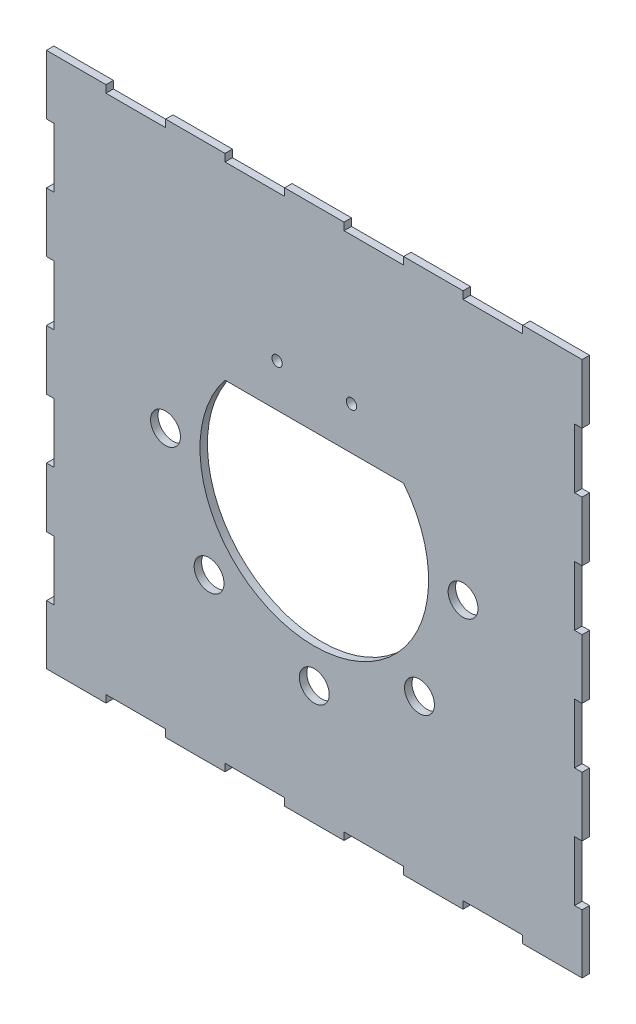
SolidWorks part; units mm, degrees
ref_plane "Front Plane" through (0, 0, 0) normal (0, 0, 1) x (1, 0, 0)
ref_plane "Top Plane" through (0, 0, 0) normal (0, 1, 0) x (1, 0, 0)
ref_plane "Right Plane" through (0, 0, 0) normal (1, 0, 0) x (0, 0, -1)
sketch "Sketch1" plane through (0, 0, 0) normal (0, 0, 1) x (1, 0, 0)
  line L0 (57.15, -57.15) -> (-57.15, 57.15) construction
  line L1 (-57.15, -57.15) -> (57.15, -57.15)
  line L2 (-57.15, -57.15) -> (-57.15, 57.15)
  line L3 (-57.15, 57.15) -> (57.15, 57.15)
  line L4 (57.15, -57.15) -> (57.15, 57.15)
  line L5 (-57.15, -57.15) -> (57.15, 57.15) construction
  point P0 (0, 0)
  point P6 (0, 0)
  dimension "D2" = 114.3
  dimension "D3" = 114.3
extrude "Boss-Extrude1" add sketch "Sketch1" along normal blind 1.5875
sketch "Sketch2" plane through (0, 0, 1.5875) normal (0, 0, 1) x (1, 0, 0)
  line L0 (-19.05, 15.24) -> (19.05, 15.24) construction
  line L1 (0, 15.24) -> (0, 0) construction
  line L2 (-19.05, 15.24) -> (19.05, 15.24)
  circle A0 centre (0, 0) radius 24.3959 construction
  arc A1 (-19.05, 15.24) -> (19.05, 15.24) centre (0, 0) ccw
  dimension "D1" = 38.1
  dimension "D2" = 15.24
extrude "Cut-Extrude1" cut sketch "Sketch2" against normal through all
sketch "Sketch4" plane through (0, 0, 1.5875) normal (0, 0, 1) x (1, 0, 0)
  line L0 (-31.75, 0) -> (31.75, 0) construction
  line L1 (0, 0) -> (-22.4506, -22.4506) construction
  line L2 (0, 0) -> (0, -31.75) construction
  line L3 (0, 0) -> (22.4506, -22.4506) construction
  circle A0 centre (0, 0) radius 31.75 construction
  circle A1 centre (-31.75, 0) radius 3.1877
  circle A2 centre (-22.4506, -22.4506) radius 3.1877
  circle A3 centre (0, -31.75) radius 3.1877
  circle A4 centre (22.4506, -22.4506) radius 3.1877
  circle A5 centre (31.75, 0) radius 3.1877
  point P6 (0, 0)
  dimension "D1" = 63.5
  dimension "D4" = 6.3754
  dimension "D2" = 45
  dimension "D3" = 45
extrude "Cut-Extrude2" cut sketch "Sketch4" against normal through all
sketch "Sketch6" plane through (0, 0, 1.5875) normal (0, 0, 1) x (1, 0, 0)
  line L20 (-57.15, 57.15) -> (-57.15, 44.45) construction
  line L21 (-57.15, 57.15) -> (-57.15, -57.15) construction
  line L22 (-57.15, 19.0246) -> (-57.15, 6.2992)
  line L23 (-57.15, 44.45) -> (-55.56, 44.45)
  line L24 (-57.15, 44.45) -> (-57.15, 31.7246)
  line L25 (-57.15, 31.7246) -> (-55.56, 31.7246)
  line L26 (-55.56, 44.45) -> (-55.56, 31.7246)
  line L27 (-57.15, 19.0246) -> (-55.56, 19.0246)
  line L28 (-55.56, 19.0246) -> (-55.56, 6.2992)
  line L29 (-57.15, 6.2992) -> (-55.56, 6.2992)
  line L30 (-57.15, -6.4008) -> (-57.15, -19.1262)
  line L31 (-57.15, -6.4008) -> (-55.56, -6.4008)
  line L32 (-55.56, -6.4008) -> (-55.56, -19.1262)
  line L33 (-57.15, -19.1262) -> (-55.56, -19.1262)
  line L34 (-57.15, -31.8262) -> (-57.15, -44.5516)
  line L35 (-57.15, -31.8262) -> (-55.56, -31.8262)
  line L36 (-55.56, -31.8262) -> (-55.56, -44.5516)
  line L37 (-57.15, -44.5516) -> (-55.56, -44.5516)
  line L38 (-57.15, 57.15) -> (-44.45, 57.15) construction
  line L39 (-55.56, 31.7246) -> (-55.56, 19.0246) construction
  line L60 (57.15, 57.15) -> (-57.15, 57.15) construction
  line L61 (57.15, 57.15) -> (57.15, 44.45) construction
  line L62 (57.15, -57.15) -> (57.15, 57.15) construction
  line L63 (57.15, 19.0246) -> (57.15, 6.2992)
  line L64 (57.15, 44.45) -> (55.56, 44.45)
  line L65 (57.15, 44.45) -> (57.15, 31.7246)
  line L66 (57.15, 31.7246) -> (55.56, 31.7246)
  line L67 (55.56, 44.45) -> (55.56, 31.7246)
  line L68 (57.15, 19.0246) -> (55.56, 19.0246)
  line L69 (55.56, 19.0246) -> (55.56, 6.2992)
  line L70 (57.15, 6.2992) -> (55.56, 6.2992)
  line L71 (57.15, -6.4008) -> (57.15, -19.1262)
  line L72 (57.15, -6.4008) -> (55.56, -6.4008)
  line L73 (55.56, -6.4008) -> (55.56, -19.1262)
  line L74 (57.15, -19.1262) -> (55.56, -19.1262)
  line L75 (57.15, -31.8262) -> (57.15, -44.5516)
  line L76 (57.15, -31.8262) -> (55.56, -31.8262)
  line L77 (55.56, -31.8262) -> (55.56, -44.5516)
  line L78 (57.15, -44.5516) -> (55.56, -44.5516)
  line L79 (55.56, 31.7246) -> (55.56, 19.0246) construction
  line L80 (-19.05, 57.15) -> (-19.05, 55.56)
  line L81 (-44.45, 57.15) -> (-31.7246, 57.15)
  line L82 (-44.45, 57.15) -> (-44.45, 55.56)
  line L83 (-44.45, 55.56) -> (-31.7246, 55.56)
  line L84 (-31.7246, 57.15) -> (-31.7246, 55.56)
  line L85 (-19.05, 57.15) -> (-6.3246, 57.15)
  line L86 (-6.3246, 57.15) -> (-6.3246, 55.56)
  line L87 (-19.05, 55.56) -> (-6.3246, 55.56)
  line L88 (6.35, 57.15) -> (6.35, 55.56)
  line L89 (6.35, 57.15) -> (19.0754, 57.15)
  line L90 (19.0754, 57.15) -> (19.0754, 55.56)
  line L91 (6.35, 55.56) -> (19.0754, 55.56)
  line L92 (31.75, 57.15) -> (31.75, 55.56)
  line L93 (31.75, 57.15) -> (44.4754, 57.15)
  line L94 (44.4754, 57.15) -> (44.4754, 55.56)
  line L95 (31.75, 55.56) -> (44.4754, 55.56)
  line L96 (-31.7246, 57.15) -> (-19.05, 57.15) construction
  line L97 (-57.15, -57.15) -> (-44.45, -57.15) construction
  line L98 (-57.15, -57.15) -> (57.15, -57.15) construction
  line L99 (-19.05, -57.15) -> (-19.05, -55.56)
  line L100 (-44.45, -57.15) -> (-31.7246, -57.15)
  line L101 (-44.45, -57.15) -> (-44.45, -55.56)
  line L102 (-44.45, -55.56) -> (-31.7246, -55.56)
  line L103 (-31.7246, -57.15) -> (-31.7246, -55.56)
  line L104 (-19.05, -57.15) -> (-6.3246, -57.15)
  line L105 (-6.3246, -57.15) -> (-6.3246, -55.56)
  line L106 (-19.05, -55.56) -> (-6.3246, -55.56)
  line L107 (6.35, -57.15) -> (6.35, -55.56)
  line L108 (6.35, -57.15) -> (19.0754, -57.15)
  line L109 (19.0754, -57.15) -> (19.0754, -55.56)
  line L110 (6.35, -55.56) -> (19.0754, -55.56)
  line L111 (31.75, -57.15) -> (31.75, -55.56)
  line L112 (31.75, -57.15) -> (44.4754, -57.15)
  line L113 (44.4754, -57.15) -> (44.4754, -55.56)
  line L114 (31.75, -55.56) -> (44.4754, -55.56)
  line L115 (-31.7246, -55.56) -> (-19.05, -55.56) construction
  dimension "D2" = 12.7
  dimension "D4" = 12.7
  dimension "D5" = 12.7254
  dimension "D6" = 1.59
  dimension "D8" = 12.7254
  dimension "D9" = 12.7
  dimension "D10" = 4
  dimension "D11" = 12.6746
  dimension "D13" = 12.7
  dimension "D14" = 1.59
  dimension "D15" = 12.7254
  dimension "D16" = 1.59
  dimension "D18" = 12.7
  dimension "D3" = 1.59
  dimension "D12" = 12.7
  dimension "D19" = 12.7254
  dimension "D21" = 12.6746
  dimension "D7" = 4
  dimension "D17" = 4
  dimension "D20" = 4
extrude "Cut-Extrude5" cut sketch "Sketch6" against normal through all
sketch "Sketch7" plane through (0, 0, 1.5875) normal (0, 0, 1) x (1, 0, 0)
  line L0 (19.05, 15.24) -> (-19.05, 15.24) construction
  line L1 (19.05, 15.24) -> (-19.05, 15.24) construction
  line L2 (0, 15.24) -> (0, 24.3675) construction
  line L3 (-7.9375, 24.3675) -> (7.9375, 24.3675) construction
  line L68 (-55.56, 44.45) -> (-55.56, 31.7246)
  line L69 (-55.56, 31.7246) -> (-57.15, 31.7246)
  line L70 (-57.15, 31.7246) -> (-57.15, 19.0246)
  line L71 (-57.15, 19.0246) -> (-55.56, 19.0246)
  line L72 (-55.56, 19.0246) -> (-55.56, 6.2992)
  line L73 (-55.56, 6.2992) -> (-57.15, 6.2992)
  line L74 (-57.15, 6.2992) -> (-57.15, -6.4008)
  line L75 (-57.15, -6.4008) -> (-55.56, -6.4008)
  line L76 (-55.56, -6.4008) -> (-55.56, -19.1262)
  line L77 (-55.56, -19.1262) -> (-57.15, -19.1262)
  line L78 (-57.15, -19.1262) -> (-57.15, -31.8262)
  line L79 (-57.15, -31.8262) -> (-55.56, -31.8262)
  line L80 (-55.56, -31.8262) -> (-55.56, -44.5516)
  line L81 (-55.56, -44.5516) -> (-57.15, -44.5516)
  line L82 (-57.15, -44.5516) -> (-57.15, -57.15)
  line L83 (-57.15, -57.15) -> (-44.45, -57.15)
  line L84 (-44.45, -57.15) -> (-44.45, -55.56)
  line L85 (-44.45, -55.56) -> (-31.7246, -55.56)
  line L86 (-31.7246, -55.56) -> (-31.7246, -57.15)
  line L87 (-31.7246, -57.15) -> (-19.05, -57.15)
  line L88 (-19.05, -57.15) -> (-19.05, -55.56)
  line L89 (-19.05, -55.56) -> (-6.3246, -55.56)
  line L90 (-6.3246, -55.56) -> (-6.3246, -57.15)
  line L91 (-6.3246, -57.15) -> (6.35, -57.15)
  line L92 (6.35, -57.15) -> (6.35, -55.56)
  line L93 (6.35, -55.56) -> (19.0754, -55.56)
  line L94 (19.0754, -55.56) -> (19.0754, -57.15)
  line L95 (19.0754, -57.15) -> (31.75, -57.15)
  line L96 (31.75, -57.15) -> (31.75, -55.56)
  line L97 (31.75, -55.56) -> (44.4754, -55.56)
  line L98 (44.4754, -55.56) -> (44.4754, -57.15)
  line L99 (44.4754, -57.15) -> (57.15, -57.15)
  line L100 (57.15, -57.15) -> (57.15, -44.5516)
  line L101 (57.15, -44.5516) -> (55.56, -44.5516)
  line L102 (55.56, -44.5516) -> (55.56, -31.8262)
  line L103 (55.56, -31.8262) -> (57.15, -31.8262)
  line L104 (57.15, -31.8262) -> (57.15, -19.1262)
  line L105 (57.15, -19.1262) -> (55.56, -19.1262)
  line L106 (55.56, -19.1262) -> (55.56, -6.4008)
  line L107 (55.56, -6.4008) -> (57.15, -6.4008)
  line L108 (57.15, -6.4008) -> (57.15, 6.2992)
  line L109 (57.15, 6.2992) -> (55.56, 6.2992)
  line L110 (55.56, 6.2992) -> (55.56, 19.0246)
  line L111 (55.56, 19.0246) -> (57.15, 19.0246)
  line L112 (57.15, 19.0246) -> (57.15, 31.7246)
  line L113 (57.15, 31.7246) -> (55.56, 31.7246)
  line L114 (55.56, 31.7246) -> (55.56, 44.45)
  line L115 (55.56, 44.45) -> (57.15, 44.45)
  line L116 (57.15, 44.45) -> (57.15, 57.15)
  line L117 (57.15, 57.15) -> (44.4754, 57.15)
  line L118 (44.4754, 57.15) -> (44.4754, 55.56)
  line L119 (44.4754, 55.56) -> (31.75, 55.56)
  line L120 (31.75, 55.56) -> (31.75, 57.15)
  line L121 (31.75, 57.15) -> (19.0754, 57.15)
  line L122 (19.0754, 57.15) -> (19.0754, 55.56)
  line L123 (19.0754, 55.56) -> (6.35, 55.56)
  line L124 (6.35, 55.56) -> (6.35, 57.15)
  line L125 (6.35, 57.15) -> (-6.3246, 57.15)
  line L126 (-6.3246, 57.15) -> (-6.3246, 55.56)
  line L127 (-6.3246, 55.56) -> (-19.05, 55.56)
  line L128 (-19.05, 55.56) -> (-19.05, 57.15)
  line L129 (-19.05, 57.15) -> (-31.7246, 57.15)
  line L130 (-31.7246, 57.15) -> (-31.7246, 55.56)
  line L131 (-31.7246, 55.56) -> (-44.45, 55.56)
  line L132 (-44.45, 55.56) -> (-44.45, 57.15)
  line L133 (-44.45, 57.15) -> (-57.15, 57.15)
  line L134 (-57.15, 57.15) -> (-57.15, 44.45)
  line L135 (-57.15, 44.45) -> (-55.56, 44.45)
  line L136 (-55.56, 44.45) -> (-55.56, 31.7246)
  line L137 (-55.56, 31.7246) -> (-57.15, 31.7246)
  line L138 (-57.15, 31.7246) -> (-57.15, 19.0246)
  line L139 (-57.15, 19.0246) -> (-55.56, 19.0246)
  line L140 (-55.56, 19.0246) -> (-55.56, 6.2992)
  line L141 (-55.56, 6.2992) -> (-57.15, 6.2992)
  line L142 (-57.15, 6.2992) -> (-57.15, -6.4008)
  line L143 (-57.15, -6.4008) -> (-55.56, -6.4008)
  line L144 (-55.56, -6.4008) -> (-55.56, -19.1262)
  line L145 (-55.56, -19.1262) -> (-57.15, -19.1262)
  line L146 (-57.15, -19.1262) -> (-57.15, -31.8262)
  line L147 (-57.15, -31.8262) -> (-55.56, -31.8262)
  line L148 (-55.56, -31.8262) -> (-55.56, -44.5516)
  line L149 (-55.56, -44.5516) -> (-57.15, -44.5516)
  line L150 (-57.15, -44.5516) -> (-57.15, -57.15)
  line L151 (-57.15, -57.15) -> (-44.45, -57.15)
  line L152 (-44.45, -57.15) -> (-44.45, -55.56)
  line L153 (-44.45, -55.56) -> (-31.7246, -55.56)
  line L154 (-31.7246, -55.56) -> (-31.7246, -57.15)
  line L155 (-31.7246, -57.15) -> (-19.05, -57.15)
  line L156 (-19.05, -57.15) -> (-19.05, -55.56)
  line L157 (-19.05, -55.56) -> (-6.3246, -55.56)
  line L158 (-6.3246, -55.56) -> (-6.3246, -57.15)
  line L159 (-6.3246, -57.15) -> (6.35, -57.15)
  line L160 (6.35, -57.15) -> (6.35, -55.56)
  line L161 (6.35, -55.56) -> (19.0754, -55.56)
  line L162 (19.0754, -55.56) -> (19.0754, -57.15)
  line L163 (19.0754, -57.15) -> (31.75, -57.15)
  line L164 (31.75, -57.15) -> (31.75, -55.56)
  line L165 (31.75, -55.56) -> (44.4754, -55.56)
  line L166 (44.4754, -55.56) -> (44.4754, -57.15)
  line L167 (44.4754, -57.15) -> (57.15, -57.15)
  line L168 (57.15, -57.15) -> (57.15, -44.5516)
  line L169 (57.15, -44.5516) -> (55.56, -44.5516)
  line L170 (55.56, -44.5516) -> (55.56, -31.8262)
  line L171 (55.56, -31.8262) -> (57.15, -31.8262)
  line L172 (57.15, -31.8262) -> (57.15, -19.1262)
  line L173 (57.15, -19.1262) -> (55.56, -19.1262)
  line L174 (55.56, -19.1262) -> (55.56, -6.4008)
  line L175 (55.56, -6.4008) -> (57.15, -6.4008)
  line L176 (57.15, -6.4008) -> (57.15, 6.2992)
  line L177 (57.15, 6.2992) -> (55.56, 6.2992)
  line L178 (55.56, 6.2992) -> (55.56, 19.0246)
  line L179 (55.56, 19.0246) -> (57.15, 19.0246)
  line L180 (57.15, 19.0246) -> (57.15, 31.7246)
  line L181 (57.15, 31.7246) -> (55.56, 31.7246)
  line L182 (55.56, 31.7246) -> (55.56, 44.45)
  line L183 (55.56, 44.45) -> (57.15, 44.45)
  line L184 (57.15, 44.45) -> (57.15, 57.15)
  line L185 (57.15, 57.15) -> (44.4754, 57.15)
  line L186 (44.4754, 57.15) -> (44.4754, 55.56)
  line L187 (44.4754, 55.56) -> (31.75, 55.56)
  line L188 (31.75, 55.56) -> (31.75, 57.15)
  line L189 (31.75, 57.15) -> (19.0754, 57.15)
  line L190 (19.0754, 57.15) -> (19.0754, 55.56)
  line L191 (19.0754, 55.56) -> (6.35, 55.56)
  line L192 (6.35, 55.56) -> (6.35, 57.15)
  line L193 (6.35, 57.15) -> (-6.3246, 57.15)
  line L194 (-6.3246, 57.15) -> (-6.3246, 55.56)
  line L195 (-6.3246, 55.56) -> (-19.05, 55.56)
  line L196 (-19.05, 55.56) -> (-19.05, 57.15)
  line L197 (-19.05, 57.15) -> (-31.7246, 57.15)
  line L198 (-31.7246, 57.15) -> (-31.7246, 55.56)
  line L199 (-31.7246, 55.56) -> (-44.45, 55.56)
  line L200 (-44.45, 55.56) -> (-44.45, 57.15)
  line L201 (-44.45, 57.15) -> (-57.15, 57.15)
  line L202 (-57.15, 57.15) -> (-57.15, 44.45)
  line L203 (-57.15, 44.45) -> (-55.56, 44.45)
  circle A0 centre (-7.9375, 24.3675) radius 1.1049
  circle A1 centre (7.9375, 24.3675) radius 1.1049
  point P16 (0, 24.3675)
  dimension "D4" = 2.2098
  dimension "D2" = 9.1275
  dimension "D3" = 15.875
  dimension "D1" = 0
extrude "Cut-Extrude6" cut sketch "Sketch7" against normal through all flip side to cut
